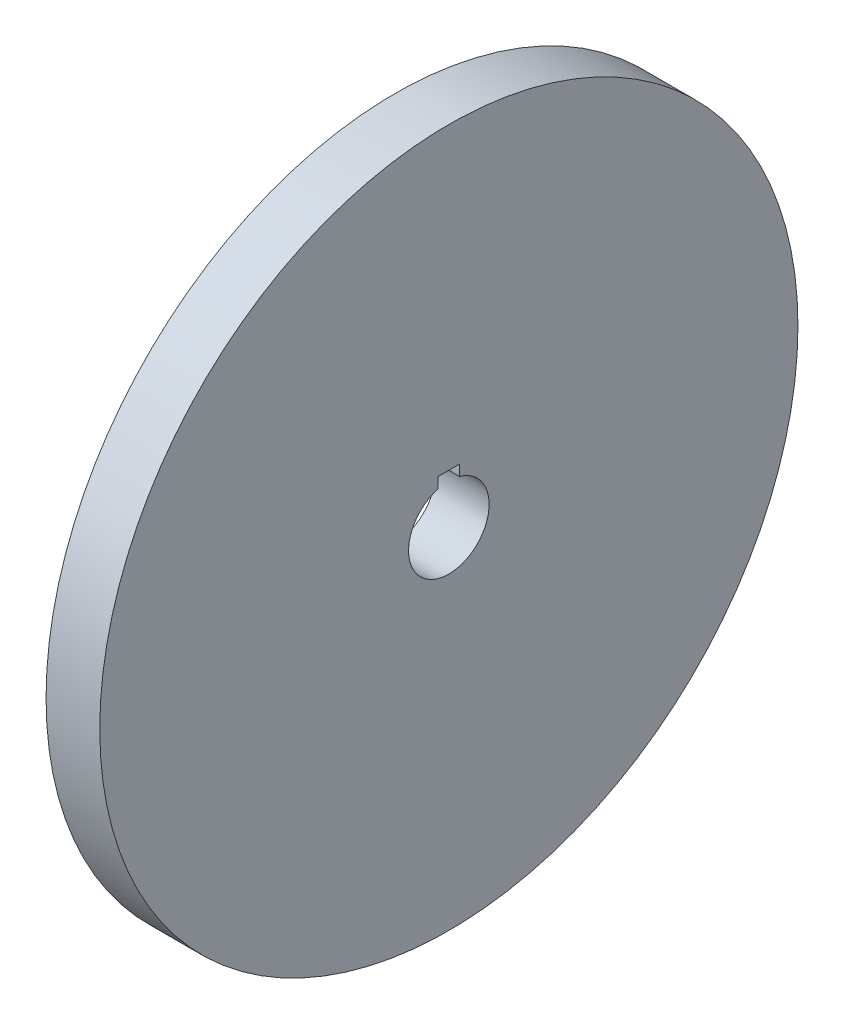
SolidWorks part; units mm, degrees
material "2024-T4"
ref_plane "Front Plane" through (0, 0, 0) normal (0, 0, 1) x (1, 0, 0)
ref_plane "Top Plane" through (0, 0, 0) normal (0, 1, 0) x (1, 0, 0)
ref_plane "Right Plane" through (0, 0, 0) normal (1, 0, 0) x (0, 0, -1)
sketch "Sketch1" plane through (0, 0, 0) normal (1, 0, 0) x (0, 0, -1)
  circle A1 centre (0, 0) radius 65
  dimension "D1" = 130
extrude "Boss-Extrude1" add sketch "Sketch1" along normal mid plane 10
sketch "Sketch3" [suppressed] plane through (5, 0, 0) normal (1, 0, 0) x (0, 0, -1)
  circle A0 centre (0, 0) radius 11
  dimension "D1" = 22
extrude "Cut-Extrude2" [suppressed] cut sketch "Sketch3" against normal through all
sketch "Sketch4" plane through (5, 0, 0) normal (1, 0, 0) x (0, 0, -1)
  circle A0 centre (0, 0) radius 7.5
  dimension "D1" = 15
extrude "Cut-Extrude3" cut sketch "Sketch4" against normal through all
sketch "Sketch5" [suppressed] plane through (5, 0, 0) normal (1, 0, 0) x (0, 0, -1)
  line L0 (0, 0) -> (0, 11) construction
  line L1 (-2, 10.8167) -> (-2, 12.8167)
  line L2 (-2, 12.8167) -> (2, 12.8167)
  line L3 (2, 10.8167) -> (2, 12.8167)
  circle A0 centre (0, 0) radius 11 construction
  arc A1 (2, 10.8167) -> (-2, 10.8167) centre (0, 0) ccw
  point P9 (0, 12.8167)
  dimension "D1" = 4
  dimension "D2" = 2
sketch "Sketch6" plane through (5, 0, 0) normal (1, 0, 0) x (0, 0, -1)
  line L0 (0, 0) -> (0, 7.5) construction
  line L1 (2, 9.2284) -> (-2, 9.2284)
  line L2 (-2, 9.2284) -> (-2, 7.2284)
  line L3 (2, 9.2284) -> (2, 7.2284)
  circle A0 centre (0, 0) radius 7.5 construction
  arc A1 (2, 7.2284) -> (-2, 7.2284) centre (0, 0) ccw
  point P8 (0, 9.2284)
  dimension "D1" = 4
  dimension "D2" = 2
extrude "Cut-Extrude4" cut sketch "Sketch6" against normal through all contours L1 L2 A1 L3
extrude "Cut-Extrude5" [suppressed] cut sketch "Sketch5" against normal through all contours L2 L3 A1 L1
sketch "Sketch7" [suppressed] plane through (5, 0, 0) normal (1, 0, 0) x (0, 0, -1)
  circle A0 centre (0, 0) radius 8
  dimension "D1" = 16
extrude "Cut-Extrude6" [suppressed] cut sketch "Sketch7" against normal through all
ref_plane "Plane1" [suppressed] through (0, 0, 0) normal (1, 0, 0) x (0, 0, -1)
sketch "Sketch8" [suppressed] plane through (0, 0, 0) normal (1, 0, 0) x (0, 0, -1)
  circle A0 centre (0, 0) radius 6.5
  circle A1 centre (0, 0) radius 8 construction
  circle A2 centre (0, 0) radius 8
  dimension "D1" = 13
extrude "Boss-Extrude2" [suppressed] add sketch "Sketch8" along normal mid plane 1.5
